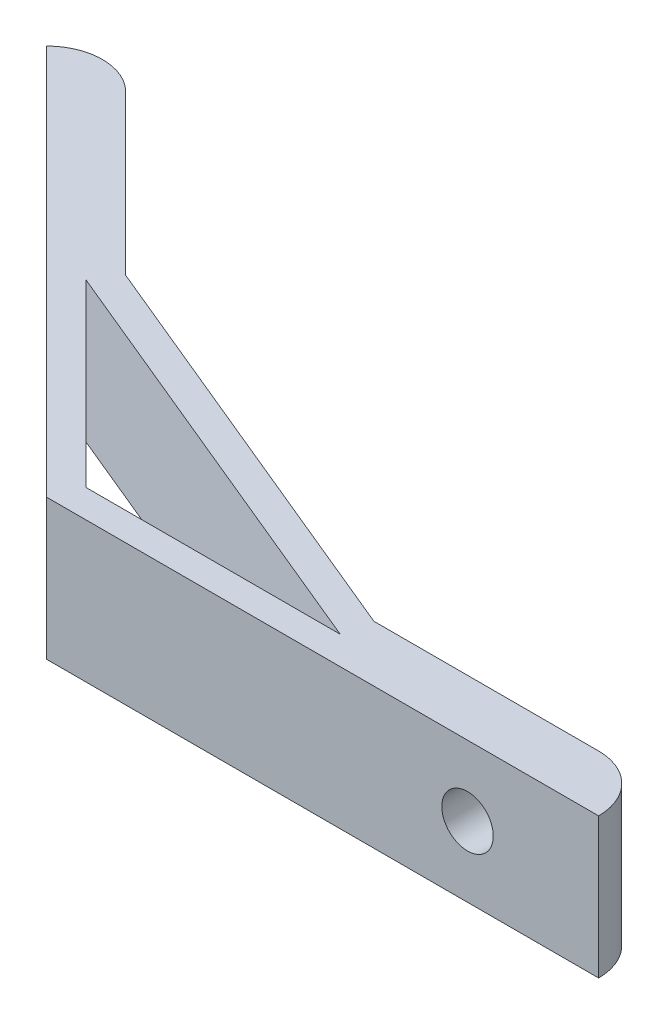
SolidWorks part; units mm, degrees
material "6063-T5"
ref_plane "Front Plane" through (0, 0, 0) normal (0, 0, 1) x (1, 0, 0)
ref_plane "Top Plane" through (0, 0, 0) normal (0, 1, 0) x (1, 0, 0)
ref_plane "Right Plane" through (0, 0, 0) normal (1, 0, 0) x (0, 0, -1)
sketch "Sketch1" plane through (0, 0, 0) normal (0, 1, 0) x (1, 0, 0)
  line L0 (0, 0) -> (-59, 0)
  line L1 (-59, 0) -> (-100.7193, 41.7193)
  line L2 (-100.7193, 41.7193) -> (-96.4767, 45.9619)
  line L7 (-96.4767, 45.9619) -> (-75.2635, 24.7487)
  line L8 (-75.2635, 24.7487) -> (-30, 6)
  line L9 (-30, 6) -> (0, 6)
  line L10 (0, 6) -> (0, 0)
  dimension "D1" = 59
  dimension "D2" = 59
  dimension "D3" = 6
  dimension "D4" = 135
  dimension "D5" = 6
  dimension "D6" = 157.5
  dimension "D7" = 30
extrude "Boss-Extrude1" add sketch "Sketch1" along normal blind 15
fillet "Fillet1" radius 6 2 edges at (-96.4767, 7.5, -45.9619) (0, 7.5, -6)
sketch "Sketch2" plane through (0, 15, 0) normal (0, 1, 0) x (1, 0, 0)
  line L0 (-76.9628, 22.2055) -> (-30.5967, 3)
  line L1 (-30.5967, 3) -> (-57.7574, 3)
  line L2 (-57.7574, 3) -> (-76.9628, 22.2055)
  line L3 (-30, 6) -> (-75.2635, 24.7487) construction
  line L4 (-59, 0) -> (0, 0) construction
  line L5 (-100.7193, 41.7193) -> (-59, 0) construction
  dimension "D1" = 3
  dimension "D2" = 3
  dimension "D3" = 3
extrude "Cut-Extrude1" cut sketch "Sketch2" against normal through all
sketch "Sketch3" plane through (0, 0, -6) normal (0, 0, -1) x (-1, 0, 0)
  line L0 (6, 15) -> (6, 0) construction
  line L1 (6, 15) -> (30, 15) construction
  circle A0 centre (14, 7.5) radius 2.75
  dimension "D1" = 5.5
  dimension "D2" = 8
  dimension "D3" = 7.5
extrude "Cut-Extrude2" cut sketch "Sketch3" against normal through all
sketch "Sketch4" plane through (-25.2574, 0, 25.2574) normal (0.7071, 0, -0.7071) x (-0.7071, 0, -0.7071)
  line L0 (70.7193, 15) -> (94.7193, 15) construction
  line L1 (94.7193, 0) -> (94.7193, 15) construction
  circle A0 centre (86.7193, 7.5) radius 2.75
  dimension "D1" = 5.5
  dimension "D2" = 7.5
  dimension "D3" = 8
extrude "Cut-Extrude3" cut sketch "Sketch4" against normal through all
